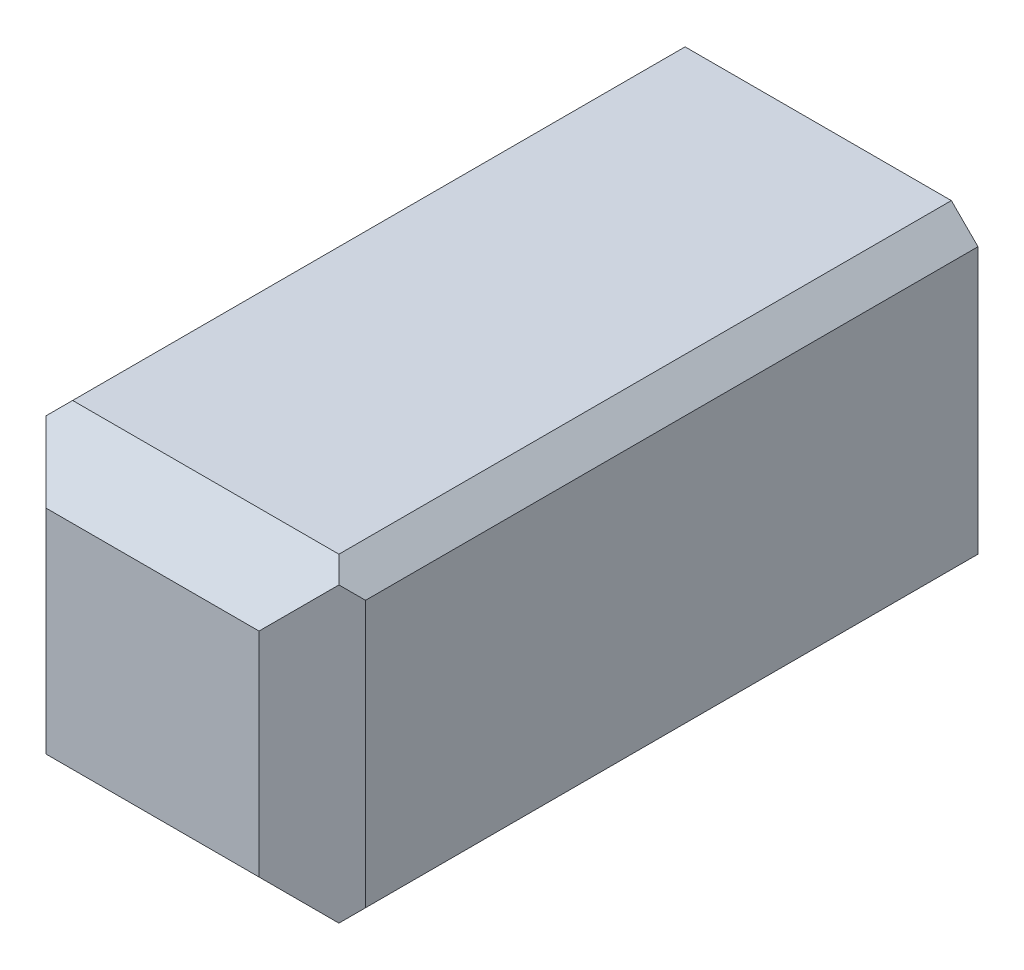
SolidWorks part; units mm, degrees
ref_plane "Front" through (0, 0, 0) normal (0, 0, 1) x (1, 0, 0)
ref_plane "Top" through (0, 0, 0) normal (0, 1, 0) x (1, 0, 0)
ref_plane "Right" through (0, 0, 0) normal (1, 0, 0) x (0, 0, -1)
sketch "Sketch2" plane through (0, 0, 0) normal (0, 0, 1) x (1, 0, 0)
  line L1 (0, 0) -> (24, 0)
  line L2 (0, 0) -> (0, 24)
  line L3 (0, 24) -> (24, 24)
  line L4 (24, 0) -> (24, 24)
  dimension "D1" = 24
  dimension "D2" = 24
extrude "Boss-Extrude2" add sketch "Sketch2" along normal blind 50
sketch "Sketch4" plane through (0, 0, 0) normal (0, 0, -1) x (-1, 0, 0)
  line L0 (-24, 0) -> (-24, 24) construction
  line L1 (-24, 24) -> (0, 24) construction
  line L2 (0, 0) -> (-24, 0) construction
  line L3 (0, 24) -> (0, 0) construction
  circle A0 centre (-21, 21) radius 1.4
  circle A1 centre (-21, 3) radius 1.4
  circle A2 centre (-3, 3) radius 1.4
  circle A3 centre (-3, 21) radius 1.4
  dimension "D3" = 3
  dimension "D5" = 3
  dimension "D9" = 2.8
  dimension "D10" = 2.8
  dimension "D11" = 2.8
  dimension "D12" = 2.8
  dimension "D1" = 3
  dimension "D2" = 3
  dimension "D4" = 3
  dimension "D6" = 3
  dimension "D7" = 3
  dimension "D8" = 3
extrude "Cut-Extrude1" cut sketch "Sketch4" against normal blind 8
chamfer "Chamfer1" distance 2 angle 45 4 edges at (0, 0, 25) (0, 24, 25) (24, 24, 25) (24, 0, 25)
chamfer "Chamfer2" distance 4 angle 45 4 edges at (12, 0, 50) (24, 12, 50) (12, 24, 50) (0, 12, 50)
